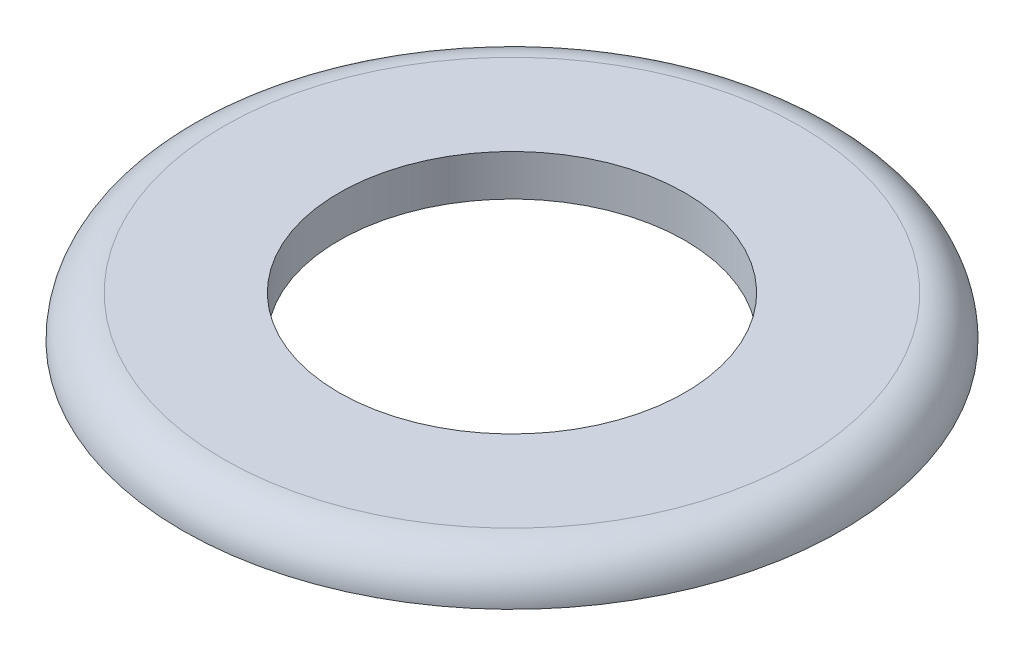
SolidWorks part; units mm, degrees
material "AISI 304"
ref_plane "Front Plane" through (0, 0, 0) normal (0, 0, 1) x (1, 0, 0)
ref_plane "Top Plane" through (0, 0, 0) normal (0, 1, 0) x (1, 0, 0)
ref_plane "Right Plane" through (0, 0, 0) normal (1, 0, 0) x (0, 0, -1)
sketch "Sketch1" plane through (0, 0, 0) normal (0, 1, 0) x (1, 0, 0)
  circle A0 centre (0, 0) radius 4
  circle A1 centre (0, 0) radius 2.1
  dimension "D1" = 8
  dimension "D2" = 4.2
extrude "Boss-Extrude1" add sketch "Sketch1" along normal blind 0.5
fillet "Fillet2" radius 0.5 1 edges at (0, 0.5, 4)
